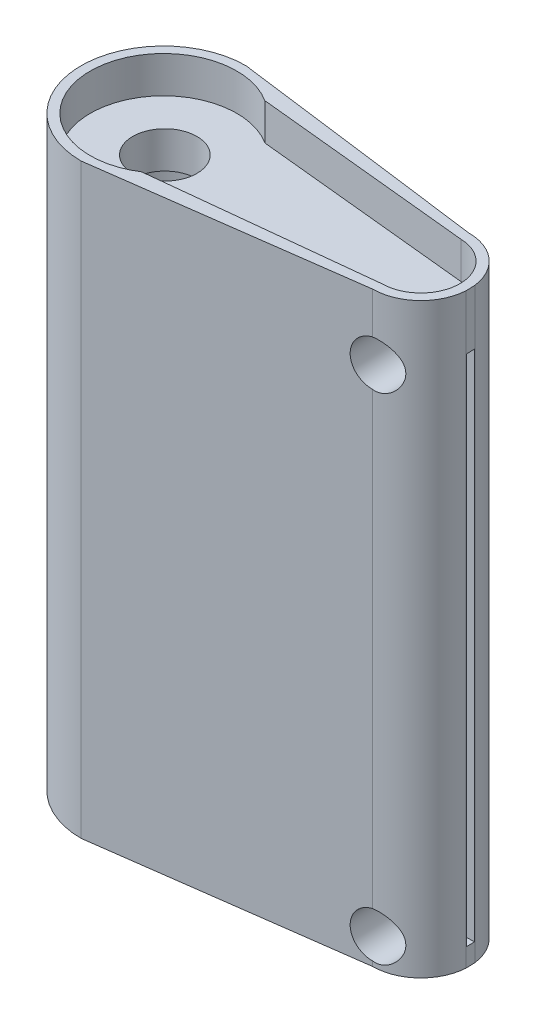
SolidWorks part; units mm, degrees
ref_plane "Front Plane" through (0, 0, 0) normal (0, 0, 1) x (1, 0, 0)
ref_plane "Top Plane" through (0, 0, 0) normal (0, 1, 0) x (1, 0, 0)
ref_plane "Right Plane" through (0, 0, 0) normal (1, 0, 0) x (0, 0, -1)
sketch "Sketch2" plane through (0, 0, 0) normal (0, 1, 0) x (1, 0, 0)
  line L0 (-24.822, 2.75) -> (-24.822, -2.75) construction
  line L1 (-26.9871, 0) -> (-9.8477, 0) construction
  line L2 (-26.9871, 4.4282) -> (-12.9872, 2.6008)
  line L3 (-26.9871, -4.5715) -> (-12.9872, -2.6725)
  line L6 (-26.9871, 0) -> (-1.9871, 0) construction
  line L9 (-10.372, 0.3) -> (-10.3556, -0.2)
  line L11 (-24.8218, 3.2918) -> (-12.9398, 2.0943)
  line L12 (-12.9872, -2.1664) -> (-24.8217, -3.4351)
  circle A1 centre (-26.9871, 0) radius 1.75
  circle A3 centre (-26.9871, -0.0716) radius 4.4998
  circle A4 centre (-12.9872, -0.0358) radius 2.6366
  circle A6 centre (-12.9872, -0.0358) radius 2.1306
  circle A7 centre (-26.9871, -0.0716) radius 4.0002
  dimension "D1" = 5.5
  dimension "D2" = 3.5
  dimension "D3" = 14
  dimension "D4" = 14
  dimension "D9" = 0
  dimension "D10" = 0
extrude "Boss-Extrude1" add sketch "Sketch2" along normal blind 30 contours A7 A1 | A7 L12 A3 L11 | A4 L11 A3 L12 | A6 L11 A4 L12 | A6 region at (-22.9198, 0, -1.6805) region at (-19.2555, 0, 0.0535) region at (-13.6394, 0, -2.1117) region at (-23.5748, 0, -1.7899) region at (-12.9872, 0, 0.0358)
extrude "Boss-Extrude2" add sketch "Sketch2<3>" along normal blind 32 contours A7 L11 A3 L12 | A4 L12 A3 | A4 A3 L11 | A6 L12 A4 L9 L11 region at (-26.4249, 0, -4.236) region at (-19.6395, 0, -3.1372) region at (-11.2892, 0, -1.8942) region at (-19.6112, 0, 3.2412)
sketch "Sketch2<3>" plane through (0, 0, 0) normal (0, 1, 0) x (1, 0, 0) same geometry as "Sketch2"
sketch "Sketch6" plane through (0, 0, 0) normal (0, -1, 0) x (1, 0, 0)
  circle A0 centre (-26.9871, 0) radius 3
extrude "Cut-Extrude3" cut sketch "Sketch6" against normal blind 28
sketch "Sketch7" plane through (-10.3511, 0, 0.3386) normal (0.9995, 0, -0.0327) x (-0.0327, 0, -0.9995)
  line L0 (0.1387, 29) -> (0.639, 29) construction
  line L3 (0.1387, 32) -> (0.1387, 0) construction
  line L4 (0.639, 32) -> (0.639, 0) construction
  line L5 (0.639, 32) -> (0.1387, 32) construction
  line L6 (0.1387, 1) -> (0.639, 1) construction
  line L7 (0.3888, 29) -> (0.3888, 1) construction
  line L8 (0.1638, 29) -> (0.6138, 29)
  line L9 (0.6138, 29) -> (0.6138, 1)
  line L10 (0.6138, 1) -> (0.1638, 1)
  line L11 (0.1638, 29) -> (0.1638, 1)
  dimension "D1" = 3
  dimension "D2" = 28
  dimension "D3" = 0.225
extrude "Cut-Extrude4" cut sketch "Sketch7" against normal blind 13
sketch "Sketch8" plane through (-0.0054, 0, -0.1638) normal (-0.0327, 0, -0.9995) x (-0.9995, 0, 0.0327)
  line L0 (12.8952, 16) -> (26.8279, 16) construction
  line L1 (12.8952, 32) -> (12.8952, 0) construction
  line L2 (26.8279, 32) -> (26.8279, 0) construction
  line L3 (12.8952, 16) -> (10.3566, 16) construction
  line L5 (10.3566, 32) -> (10.3566, 0) construction
  line L6 (26.8279, 32) -> (12.8952, 32) construction
  line L7 (26.8279, 0) -> (12.8952, 0) construction
  circle A0 centre (12.8952, 28.5) radius 1.25
  circle A1 centre (12.8952, 1.5) radius 1.25
  dimension "D1" = 27
  dimension "D2" = 3.5
  dimension "D3" = 1.5
extrude "Cut-Extrude5" cut sketch "Sketch8" against normal through all contours A0 | A0 | A1 region at (-12.8936, 28.5, 0.2579)
extrude "Cut-Extrude6" cut sketch "Sketch8<3>" along normal through all
sketch "Sketch8<3>" plane through (-0.0054, 0, -0.1638) normal (-0.0327, 0, -0.9995) x (-0.9995, 0, 0.0327) same geometry as "Sketch8"
